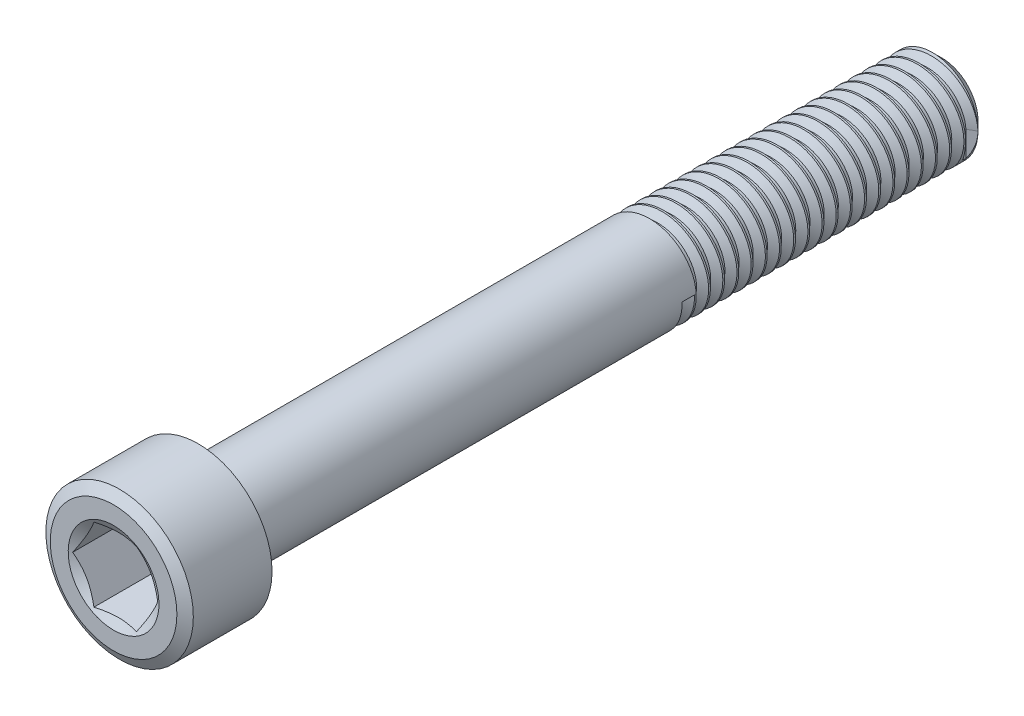
SolidWorks part; units mm, degrees
material "Stainless Steel (ferritic)"
ref_plane "Front Plane" through (0, 0, 0) normal (0, 0, 1) x (1, 0, 0)
ref_plane "Top Plane" through (0, 0, 0) normal (0, 1, 0) x (1, 0, 0)
ref_plane "Right Plane" through (0, 0, 0) normal (1, 0, 0) x (0, 0, -1)
sketch "Sketch1" plane through (0, 0, 0) normal (1, 0, 0) x (0, 0, -1)
  line L0 (0, 0) -> (66.2642, 0) construction
  line L1 (0, 0) -> (0, 5.582)
  line L2 (0, 5.582) -> (0.53, 6.5)
  line L3 (0.53, 6.5) -> (7.47, 6.5)
  line L4 (7.47, 6.5) -> (8, 5.582)
  line L5 (8, 5.582) -> (8, 4)
  line L6 (8, 4) -> (73, 4)
  line L7 (73, 4) -> (73, 0)
  line L8 (73, 0) -> (0, 0)
  dimension "D1" = 4
  dimension "D2" = 65
  dimension "D3" = 8
  dimension "D4" = 6.5
  dimension "D5" = 30
  dimension "D6" = 30
  dimension "D7" = 0.53
  dimension "D8" = 0.53
revolve "Revolve1" add sketch "Sketch1" angle 360 about L0
chamfer "Chamfer1" distance 0.8 angle 45 1 edges at (4, 0, -73)
sketch "Sketch2" plane through (0, 0, 0) normal (0, 0, 1) x (1, 0, 0)
  line L1 (-1.8764, -3.25) -> (1.8764, -3.25)
  line L2 (1.8764, -3.25) -> (3.7528, 0)
  line L3 (3.7528, 0) -> (1.8764, 3.25)
  line L4 (1.8764, 3.25) -> (-1.8764, 3.25)
  line L5 (-1.8764, 3.25) -> (-3.7528, 0)
  line L6 (-3.7528, 0) -> (-1.8764, -3.25)
  circle A0 centre (0, 0) radius 3.25 construction
  dimension "D1" = 6.5
extrude "Cut-Extrude1" cut sketch "Sketch2" against normal blind 6
sketch "Sketch3" plane through (0, 0, 0) normal (1, 0, 0) x (0, 0, -1)
  line L0 (0, 0) -> (40.9537, 0) construction
  line L1 (0, 0) -> (0, 4)
  line L2 (0, 5.582) -> (0, -5.582) construction
  line L3 (0, 4) -> (2.3094, 0)
  line L4 (2.3094, 0) -> (0, 0)
  line L5 (6, 3.25) -> (6, 0)
  line L6 (6, 0) -> (7.8764, 0)
  line L7 (7.8764, 0) -> (6, 3.25)
  dimension "D1" = 30
  dimension "D2" = 30
  dimension "D3" = 4
revolve "Cut-Revolve1" cut sketch "Sketch3" angle 360 about L0
thread "Thread1" pitch 1.25 method cut profile "Thread Profile2" start angle 0, offset 0, length 25, pitch 1.25, diameter 8
ref_plane "Plane2" through (4, 0, -72.2) normal (0, -1, 0) x (1, 0, 0)
sketch "Thread Profile2" plane through (4, 0, -72.2) normal (0, -1, 0) x (1, 0, 0)
  line L0 (0, 0) -> (0, 1.25) construction
  line L11 (0, 0) -> (0, 1.0937)
  line L12 (0, 1.0937) -> (-0.6766, 0.7031)
  line L13 (-0.6766, 0.7031) -> (-0.6766, 0.3906)
  line L15 (-0.6766, 0.3906) -> (0, 0)
  line L17 (-0.6766, 0.5469) -> (0, 0.5469) construction
  point P2 (0, 0)
  dimension "Pitch" = 1.25
  dimension "Profile_Angle" = 60
  dimension "Profile_Land" = 0.3125
  dimension "Profile_Height" = 0.6766
sketch "Sketch20" plane through (0, 0, 0) normal (0, 1, 0) x (1, 0, 0)
  line L4 (4, 72.2) -> (3.3234, 71.8094)
  line L5 (3.3234, 71.8094) -> (3.3234, 71.4969)
  line L6 (3.3234, 71.4969) -> (4, 71.1063)
  line L7 (4, 71.1063) -> (4, 72.2)
  line L8 (4, 72.2) -> (3.3234, 71.8094)
  line L9 (3.3234, 71.8094) -> (3.3234, 71.4969)
  line L10 (3.3234, 71.4969) -> (4, 71.1063)
  line L11 (4, 71.1063) -> (4, 72.2)
  dimension "D1" = 0
extrude "Cut-Extrude2" cut sketch "Sketch20" against normal blind 10
